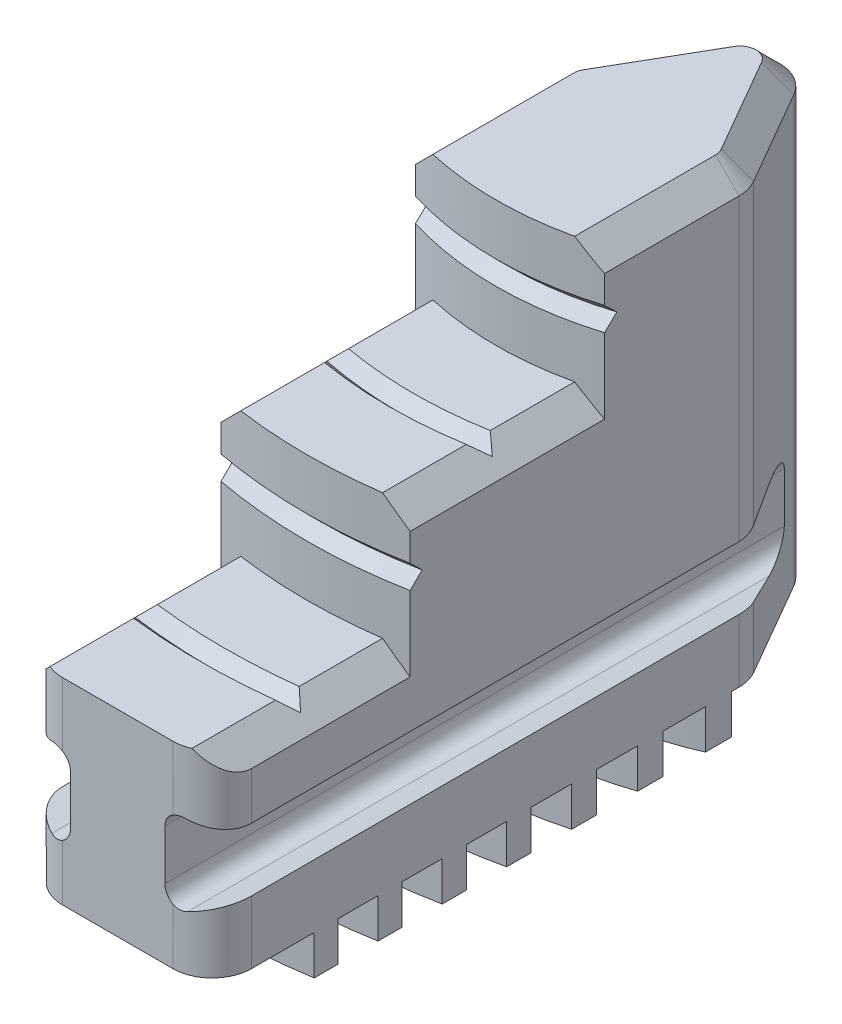
SolidWorks part; units mm, degrees
ref_plane "Front Plane" through (0, 0, 0) normal (0, 0, 1) x (1, 0, 0)
ref_plane "Top Plane" through (0, 0, 0) normal (0, 1, 0) x (1, 0, 0)
ref_plane "Right Plane" through (0, 0, 0) normal (1, 0, 0) x (0, 0, -1)
sketch "Sketch1" plane through (0, 0, 0) normal (0, 1, 0) x (1, 0, 0)
  line L0 (0, 0) -> (0, 89) construction
  line L1 (0, 0) -> (-12, 0)
  line L2 (-12, 0) -> (-12, 68.2154)
  line L3 (-12, 68.2154) -> (0, 89)
  line L4 (0, 89) -> (12, 68.2154)
  line L5 (12, 68.2154) -> (12, 0)
  line L6 (12, 0) -> (0, 0)
  dimension "D1" = 89
  dimension "D2" = 24
  dimension "D3" = 12
  dimension "D4" = 30
  dimension "D5" = 30
extrude "Boss-Extrude1" add sketch "Sketch1" along normal blind 62
sketch "Sketch3" plane through (0, 0, 0) normal (1, 0, 0) x (0, 0, -1)
  line L1 (89, 0) -> (63, 0)
  line L2 (89, 0) -> (89, 5)
  line L3 (89, 5) -> (63, 5)
  line L4 (-16, 0) -> (-16, 5)
  line L6 (60, 5) -> (60, 0)
  line L8 (63, 5) -> (63, 0)
  line L9 (52, 5) -> (52, 0)
  line L11 (55, 5) -> (55, 0)
  line L13 (44, 5) -> (44, 0)
  line L15 (47, 5) -> (47, 0)
  line L17 (36, 5) -> (36, 0)
  line L19 (39, 5) -> (39, 0)
  line L21 (28, 5) -> (28, 0)
  line L23 (31, 5) -> (31, 0)
  line L25 (20, 5) -> (20, 0)
  line L27 (23, 5) -> (23, 0)
  line L29 (12, 5) -> (12, 0)
  line L31 (15, 5) -> (15, 0)
  line L32 (12, 5) -> (-16, 5)
  line L34 (12, 0) -> (-16, 0)
  line L36 (20, 0) -> (15, 0)
  line L38 (20, 5) -> (15, 5)
  line L41 (28, 5) -> (23, 5)
  line L43 (28, 0) -> (23, 0)
  line L44 (36, 0) -> (31, 0)
  line L46 (36, 5) -> (31, 5)
  line L49 (44, 5) -> (39, 5)
  line L51 (44, 0) -> (39, 0)
  line L52 (52, 0) -> (47, 0)
  line L54 (52, 5) -> (47, 5)
  line L56 (60, 5) -> (55, 5)
  line L57 (60, 0) -> (55, 0)
  dimension "D1" = 5
  dimension "D2" = 105
  dimension "D3" = 3
  dimension "D4" = 26
  dimension "D6" = 5
  dimension "D5" = 7
revolve "Cut-Revolve1" cut sketch "Sketch3" angle 360 about axis through (0, 62, -89) along (0, -1, 0)
sketch "Sketch4" plane through (0, 0, 0) normal (1, 0, 0) x (0, 0, -1)
  line L0 (-19, 30) -> (24, 30)
  line L1 (34.5, 46) -> (36, 44.5)
  line L2 (24, 30) -> (24, 46)
  line L3 (24, 46) -> (48, 46)
  line L4 (48, 46) -> (48, 62)
  line L5 (0, 62) -> (68.2154, 62) construction
  line L6 (-19, 30) -> (-19, 62)
  line L7 (-19, 62) -> (48, 62)
  line L8 (0, 5) -> (12.9408, 5) construction
  line L9 (36, 44.5) -> (37.5, 46)
  line L10 (89, 62) -> (89, 5) construction
  line L11 (0, 62) -> (0, 5) construction
  line L12 (10.5, 30) -> (12, 28.5)
  line L13 (12, 28.5) -> (13.5, 30)
  line L14 (13.5, 30) -> (10.5, 30)
  line L15 (12, 30) -> (12, 28.5) construction
  line L16 (0, 30) -> (0, 62) construction
  line L17 (37.5, 46) -> (34.5, 46)
  line L18 (36, 46) -> (36, 44.5) construction
  line L22 (24, 39.5) -> (24, 36.5)
  line L23 (24, 36.5) -> (25.5, 38)
  line L24 (25.5, 38) -> (24, 39.5)
  line L25 (24, 38) -> (25.5, 38) construction
  line L26 (48, 55.5) -> (48, 52.5)
  line L27 (48, 52.5) -> (49.5, 54)
  line L28 (49.5, 54) -> (48, 55.5)
  line L29 (48, 54) -> (49.5, 54) construction
  point P33 (24, 38)
  point P34 (48, 54)
  dimension "D1" = 16
  dimension "D2" = 16
  dimension "D3" = 25
  dimension "D4" = 24
  dimension "D5" = 24
  dimension "D6" = 41
  dimension "D7" = 67
  dimension "D8" = 90
  dimension "D9" = 1.5
  dimension "D10" = 12
  dimension "D11" = 90
  dimension "D12" = 1.5
  dimension "D13" = 45
  dimension "D14" = 90
  dimension "D15" = 1.5
  dimension "D16" = 45
  dimension "D17" = 90
  dimension "D18" = 1.5
revolve "Cut-Revolve2" cut sketch "Sketch4" angle 360 about axis through (0, 62, -89) along (0, -1, 0) region at (0, 47.7455, -9.8091)
sketch "Sketch5" plane through (0, 0, 0) normal (0, 0, 1) x (1, 0, 0)
  line L0 (8, 20.1641) -> (8, 13.8359) construction
  line L1 (10, 20.1641) -> (10, 13.8359)
  line L2 (6, 20.1641) -> (6, 13.8359)
  line L3 (8.6014, 22.0716) -> (12, 21)
  line L4 (12, 30) -> (12, 5) construction
  line L5 (8.6014, 11.9284) -> (12, 13)
  line L6 (8, 17) -> (12, 17) construction
  line L7 (12, 21) -> (12, 13)
  line L8 (-12, 5) -> (12, 5) construction
  arc A0 (10, 20.1641) -> (6, 20.1641) centre (8, 20.1641) ccw
  arc A1 (6, 13.8359) -> (10, 13.8359) centre (8, 13.8359) ccw
  point P2 (8, 17)
  line M6 (12, 5) -> (12, 30)
  dimension "D1" = 2
  dimension "D2" = 35
  dimension "D3" = 17.5
  dimension "D4" = 8
  dimension "D5" = 6
  dimension "D6" = 8
fillet "Fillet2" radius 5 5 edges at (0, 33.5, -89) (-12, 33.5, -68.2154) (12, 33.5, -68.2154) (12, 17.5, 0) (-12, 17.5, 0)
extrude "Cut-Extrude2" cut sketch "Sketch5" against normal through all contours A1 L5 L3 A0 L1 M6 | L2 A1 L1 A0 region at (10.9188, 17, 0) region at (8, 17, 0)
mirror "Mirror2" about plane through (0, 0, 0) normal (1, 0, 0) of "Cut-Extrude2"
chamfer "Chamfer1" distance 3 angle 45 11 edges at (-12, 62, -58.3355) (-11.8296, 62, -68.1697) (-7.8301, 62, -75.4378) (0, 62, -84) (7.8301, 62, -75.4378) (11.8296, 62, -68.1697) (12, 62, -58.3355) (12, 46, -30.4774) (12, 30, -19.7885) (-12, 30, -19.7885) (-12, 46, -30.4774)
